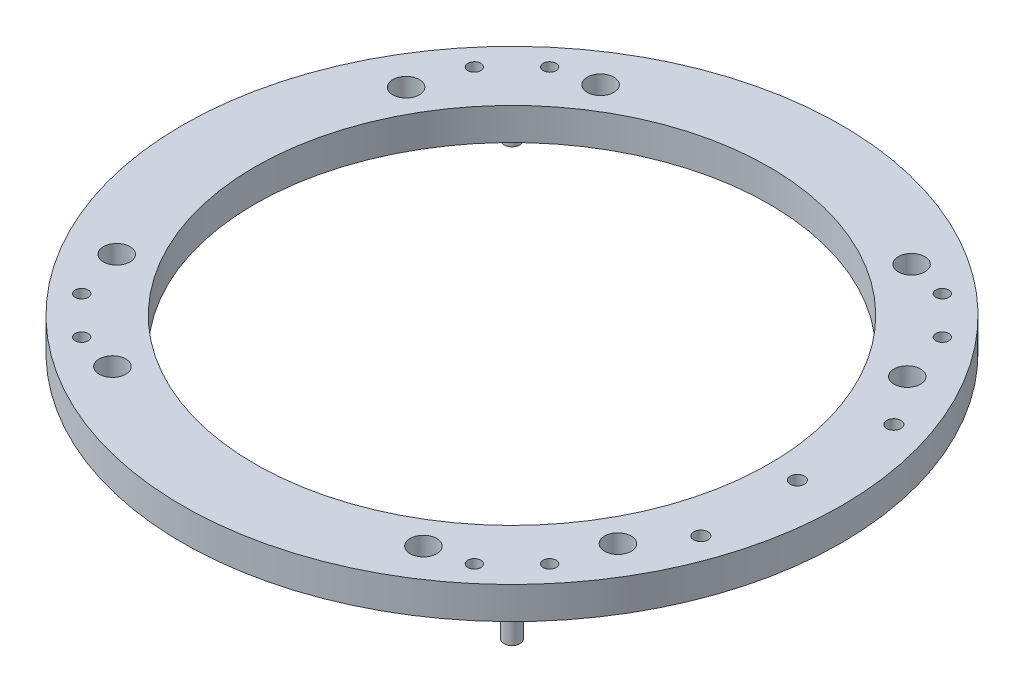
SolidWorks part; units mm, degrees
ref_plane "Front Plane" through (0, 0, 0) normal (0, 0, 1) x (1, 0, 0)
ref_plane "Top Plane" through (0, 0, 0) normal (0, 1, 0) x (1, 0, 0)
ref_plane "Right Plane" through (0, 0, 0) normal (1, 0, 0) x (0, 0, -1)
sketch "Sketch1" plane through (0, 0, 0) normal (0, 0, 1) x (1, 0, 0)
  line L0 (0, 1125.8152) -> (0, -48874.1848) construction
  line L1 (101.6, 1057.275) -> (114.3, 1057.275)
  line L3 (104.775, 955.675) -> (114.3, 955.675) construction
  line L4 (114.3, 1057.275) -> (114.3, 955.675) construction
  line L9 (101.6, 1069.975) -> (130.175, 1069.975)
  line L10 (101.6, 1069.975) -> (101.6, 1057.275)
  line L11 (101.6, 1057.275) -> (130.175, 1057.275)
  line L12 (130.175, 1069.975) -> (130.175, 1057.275)
  line L13 (104.775, 1057.275) -> (104.775, 955.675) construction
  line L14 (104.775, 1044.575) -> (104.775, 1057.275) construction
  line L15 (104.775, 968.375) -> (104.775, 955.675) construction
  line L16 (130.175, 955.675) -> (101.6, 955.675) construction
revolve "Revolve1" add sketch "Sketch1" angle 360 about L0 region at (115.8875, 1063.625, 0)
sketch "Sketch5" [suppressed] plane through (0, 1057.275, 0) normal (0, -1, 0) x (1, 0, 0)
  line L0 (0, 0) -> (107.3882, 47.625) construction
  line L1 (0, 0) -> (107.3882, -47.625) construction
  line L2 (0, 0) -> (117.475, 0) construction
  line L3 (107.3882, -47.625) -> (96.8765, -47.625)
  line L4 (107.3882, 47.625) -> (96.8765, 47.625)
  circle A0 centre (0, 0) radius 107.95 construction
  circle A1 centre (0, 0) radius 117.475
  arc A2 (107.3882, -47.625) -> (107.3882, 47.625) centre (0, 0) ccw
  circle A3 centre (0, 0) radius 107.95
  arc A4 (96.8765, -47.625) -> (96.8765, 47.625) centre (0, 0) ccw
  circle A5 centre (0, 0) radius 117.475 construction
  dimension "D3" = 95.25
  dimension "D1" = 0
  dimension "D2" = 0
extrude "Cut-Extrude1" [suppressed] cut sketch "Sketch5" along normal through all flip side to cut
sketch "Sketch11" [suppressed] plane through (0, 1057.275, 0) normal (0, -1, 0) x (1, 0, 0)
  line L0 (117.475, 47.625) -> (117.475, -47.625)
  line L1 (117.475, 47.625) -> (107.3882, 47.625)
  line L2 (107.3882, -47.625) -> (117.475, -47.625)
  arc A1 (107.3882, -47.625) -> (107.3882, 47.625) centre (0, 0) ccw construction
  arc A2 (107.3882, -47.625) -> (107.3882, 47.625) centre (0, 0) ccw
  point P3 (117.475, 0)
extrude "Boss-Extrude2" [suppressed] add sketch "Sketch11" along normal up to surface (101.6 mm away)
sketch "Sketch2" [suppressed] plane through (0, 0, 0) normal (0, 0, 1) x (1, 0, 0)
  line L0 (65.7096, 1044.575) -> (117.475, 1044.575)
  line L1 (117.475, 1044.575) -> (117.475, 1006.475)
  line L2 (184.3824, 1006.475) -> (0, 1006.475) construction
  line L3 (117.475, 1006.475) -> (65.7096, 1006.475)
  line L4 (65.7096, 1006.475) -> (65.7096, 1044.575)
  line L5 (184.3824, 1006.475) -> (0, 1006.475) construction
revolve "Cut-Revolve2" [suppressed] cut sketch "Sketch2" angle 360 about L5
sketch "Sketch6" plane through (0, 1057.275, 0) normal (0, -1, 0) x (1, 0, 0)
  line L0 (-85.3124, -85.3124) -> (85.3124, 85.3124) construction
  line L1 (-85.3124, 85.3124) -> (85.3124, -85.3124) construction
  line L2 (0, 0) -> (0, 120.65) construction
  circle A0 centre (0, 0) radius 120.65 construction
  circle A1 centre (-85.3124, 85.3124) radius 3.175
  circle A2 centre (85.3124, 85.3124) radius 3.175
  circle A3 centre (85.3124, -85.3124) radius 3.175
  circle A4 centre (-85.3124, -85.3124) radius 3.175
  point P5 (0, 0)
  point P8 (0, 0)
  dimension "D2" = 241.3
  dimension "D3" = 6.35
  dimension "D1" = 45
extrude "Boss-Extrude1" add sketch "Sketch6" along normal blind 12.7
hole_wizard "1/4-20 Tapped Hole1" positions "Sketch9" profile "Sketch10" tap size "1/4-20" standard "ANSI Inch" end condition through all
sketch "Sketch9" plane through (0, 1057.275, 0) normal (0, -1, 0) x (-1, 0, 0)
  line L0 (0, 0) -> (85.3124, 85.3124) construction
  line L3 (0, 0) -> (77.5523, 92.4233) construction
  arc A0 (77.5523, 92.4233) -> (92.4233, 77.5523) centre (0, 0) cw
  point P0 (77.5523, 92.4233)
  point P2 (92.4233, 77.5523)
  dimension "D1" = 5
sketch "Sketch10" plane through (-77.5523, 1057.275, -92.4233) normal (1, 0, 0) x (0, 0, -1)
  line L0 (0, 0) -> (0, 12.7)
  line L1 (0, 12.7) -> (2.5527, 12.7)
  line L2 (2.5527, 12.7) -> (2.5527, 0)
  line L5 (2.5527, 0) -> (0, 0)
  line L11 (0, -6.35) -> (0, 107.95) construction
  dimension "Thru Tap Drill Dia." = 5.1054
  dimension "Thru Tap Drill Depth" = 12.7
cosmetic thread "Hole Thread1" parameters "D2"=6.35
cosmetic thread "Hole Thread2" parameters "D2"=6.35
pattern_circular "CirPattern1" count 4 over 360 about axis through (0, 1125.8152, 0) along (0, 1, 0) of "1/4-20 Tapped Hole1"
ref_plane "Plane1" through (0, 1063.625, 0) normal (0, 1, 0) x (1, 0, 0)
sketch "Sketch12" plane through (0, 1063.625, 0) normal (0, 1, 0) x (1, 0, 0)
  line L0 (55.5625, -96.2371) -> (-55.5625, 96.2371) construction
  line L1 (55.5625, 96.2371) -> (-55.5625, -96.2371) construction
  line L2 (0, 0) -> (-111.125, 0) construction
  line L3 (-65.8243, -101.311) -> (-56.2993, -84.8132)
  line L4 (-65.8243, -101.311) -> (-54.8257, -107.661)
  line L5 (-56.2993, -84.8132) -> (-45.3007, -91.1632)
  line L6 (-54.8257, -107.661) -> (-45.3007, -91.1632)
  line L7 (-65.8243, -101.311) -> (-45.3007, -91.1632) construction
  line L8 (-56.2993, -84.8132) -> (-54.8257, -107.661) construction
  line L9 (-54.8257, 107.661) -> (-45.3007, 91.1632)
  line L10 (-54.8257, 107.661) -> (-65.8243, 101.311)
  line L11 (-45.3007, 91.1632) -> (-56.2993, 84.8132)
  line L12 (-65.8243, 101.311) -> (-56.2993, 84.8132)
  line L13 (-54.8257, 107.661) -> (-56.2993, 84.8132) construction
  line L14 (-45.3007, 91.1632) -> (-65.8243, 101.311) construction
  line L15 (0, 0) -> (0, 130.175) construction
  line L16 (45.3007, 91.1632) -> (65.8243, 101.311) construction
  line L17 (54.8257, 107.661) -> (56.2993, 84.8132) construction
  line L18 (56.2993, -84.8132) -> (54.8257, -107.661) construction
  line L19 (65.8243, -101.311) -> (45.3007, -91.1632) construction
  line L20 (65.8243, 101.311) -> (56.2993, 84.8132)
  line L21 (45.3007, 91.1632) -> (56.2993, 84.8132)
  line L22 (54.8257, 107.661) -> (65.8243, 101.311)
  line L23 (54.8257, 107.661) -> (45.3007, 91.1632)
  line L24 (54.8257, -107.661) -> (45.3007, -91.1632)
  line L25 (56.2993, -84.8132) -> (45.3007, -91.1632)
  line L26 (65.8243, -101.311) -> (54.8257, -107.661)
  line L27 (65.8243, -101.311) -> (56.2993, -84.8132)
  circle A0 centre (0, 0) radius 111.125 construction
  circle A1 centre (0, 0) radius 130.175 construction
  circle A3 centre (0, 0) radius 101.6 construction
  point P6 (0, 0)
  point P8 (0, 0)
  dimension "D1" = 60
  dimension "D3" = 19.05
  dimension "D4" = 12.7
extrude "Boss-Extrude3" [suppressed] add sketch "Sketch12" along normal mid plane 76.2
fillet "Fillet1" [suppressed] type full round
chamfer "Chamfer1" [suppressed] distance 15.875 angle 32.5
fillet "Fillet2" [suppressed] radius 6.35
fillet "Fillet3" [suppressed] radius 12.7
hole_wizard "#10 Clearance Hole1" positions "Sketch14" profile "Sketch15" hole size "#10" standard "ANSI Inch" end condition through all
sketch "Sketch14" plane through (0, 1069.975, 0) normal (0, 1, 0) x (1, 0, 0)
  point P0 (112.7125, 38.1)
  point P3 (112.7125, 0)
  point P6 (112.7125, -38.1)
sketch "Sketch15" plane through (112.7125, 1069.975, -38.1) normal (1, 0, 0) x (0, 0, 1)
  line L0 (0, 0) -> (0, 25.4)
  line L1 (0, 25.4) -> (2.8067, 25.4)
  line L2 (2.8067, 25.4) -> (2.8067, 0)
  line L5 (2.8067, 0) -> (0, 0)
  line L11 (0, -6.35) -> (0, 107.95) construction
  dimension "Thru Hole Dia." = 5.6134
  dimension "Thru Hole Depth" = 25.4
hole_wizard "Z (0.413) Diameter Hole1" positions "Sketch16" profile "Sketch17" hole size "Z" standard "ANSI Inch" end condition through all
sketch "Sketch16" plane through (0, 1069.975, 0) normal (0, 1, 0) x (1, 0, 0)
  line L0 (-98.9867, -57.15) -> (98.9867, 57.15) construction
  line L4 (98.9867, -57.15) -> (-98.9867, 57.15) construction
  line L6 (0, 0) -> (0, 114.3) construction
  line L8 (-61.4133, -96.3996) -> (61.4133, 96.3996) construction
  line L11 (-61.4133, 96.3996) -> (61.4133, -96.3996) construction
  circle A0 centre (0, 0) radius 114.3 construction
  point P0 (-98.9867, -57.15)
  point P2 (98.9867, -57.15)
  point P4 (98.9867, 57.15)
  point P6 (-98.9867, 57.15)
  point P37 (-61.4133, 96.3996)
  point P39 (61.4133, 96.3996)
  point P41 (61.4133, -96.3996)
  point P43 (-61.4133, -96.3996)
  dimension "D2" = 228.6
  dimension "D1" = 120
  dimension "D3" = 65
sketch "Sketch17" plane through (-98.9867, 1069.975, 57.15) normal (1, 0, 0) x (0, 0, 1)
  line L0 (0, 0) -> (0, 25.4)
  line L1 (0, 25.4) -> (5.2451, 25.4)
  line L2 (5.2451, 25.4) -> (5.2451, 0)
  line L5 (5.2451, 0) -> (0, 0)
  line L11 (0, -6.35) -> (0, 107.95) construction
  dimension "Thru Hole Dia." = 10.4902
  dimension "Thru Hole Depth" = 25.4
